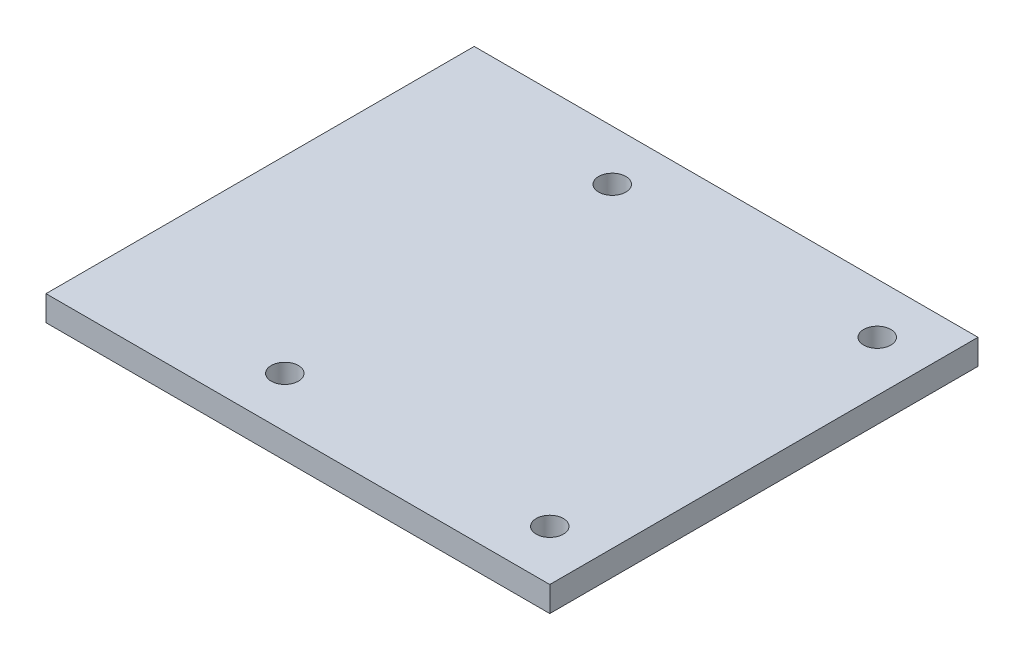
SolidWorks part; units mm, degrees
material "6061 Alloy"
ref_plane "Front Plane" through (0, 0, 0) normal (0, 0, 1) x (1, 0, 0)
ref_plane "Top Plane" through (0, 0, 0) normal (0, 1, 0) x (1, 0, 0)
ref_plane "Right Plane" through (0, 0, 0) normal (1, 0, 0) x (0, 0, -1)
sketch "Sketch1" plane through (0, 0, 0) normal (0, 1, 0) x (1, 0, 0)
  line L1 (-63.5, 53.975) -> (63.5, 53.975)
  line L2 (-63.5, 53.975) -> (-63.5, -53.975)
  line L3 (-63.5, -53.975) -> (63.5, -53.975)
  line L4 (63.5, 53.975) -> (63.5, -53.975)
  line L5 (-63.5, 53.975) -> (63.5, -53.975) construction
  line L6 (-63.5, -53.975) -> (63.5, 53.975) construction
  point P0 (0, 0)
  dimension "D1" = 107.95
  dimension "D2" = 127
extrude "Boss-Extrude1" add sketch "Sketch1" along normal blind 6.35
sketch "Sketch3" plane through (0, 0, 0) normal (0, -1, 0) x (1, 0, 0)
  line L0 (17.399, 0) -> (17.399, -20.7585) construction
  line L1 (0, 0) -> (-13.1006, 0) construction
  line L3 (-63.5, 53.975) -> (63.5, 53.975) construction
  line L4 (63.5, -53.975) -> (-63.5, -53.975) construction
  line L5 (63.5, 53.975) -> (63.5, -53.975) construction
  line L6 (63.5, 53.975) -> (63.5, -53.975) construction
  circle A0 centre (-16.002, 41.275) radius 3.429
  circle A1 centre (-16.002, -41.275) radius 3.429
  circle A2 centre (50.8, 41.275) radius 3.429
  circle A3 centre (50.8, -41.275) radius 3.429
  dimension "D1" = 79.502
  dimension "D4" = 12.7
  dimension "D2" = 12.7
  dimension "D3" = 12.7
extrude "Cut-Extrude2" cut sketch "Sketch3" against normal up to next
